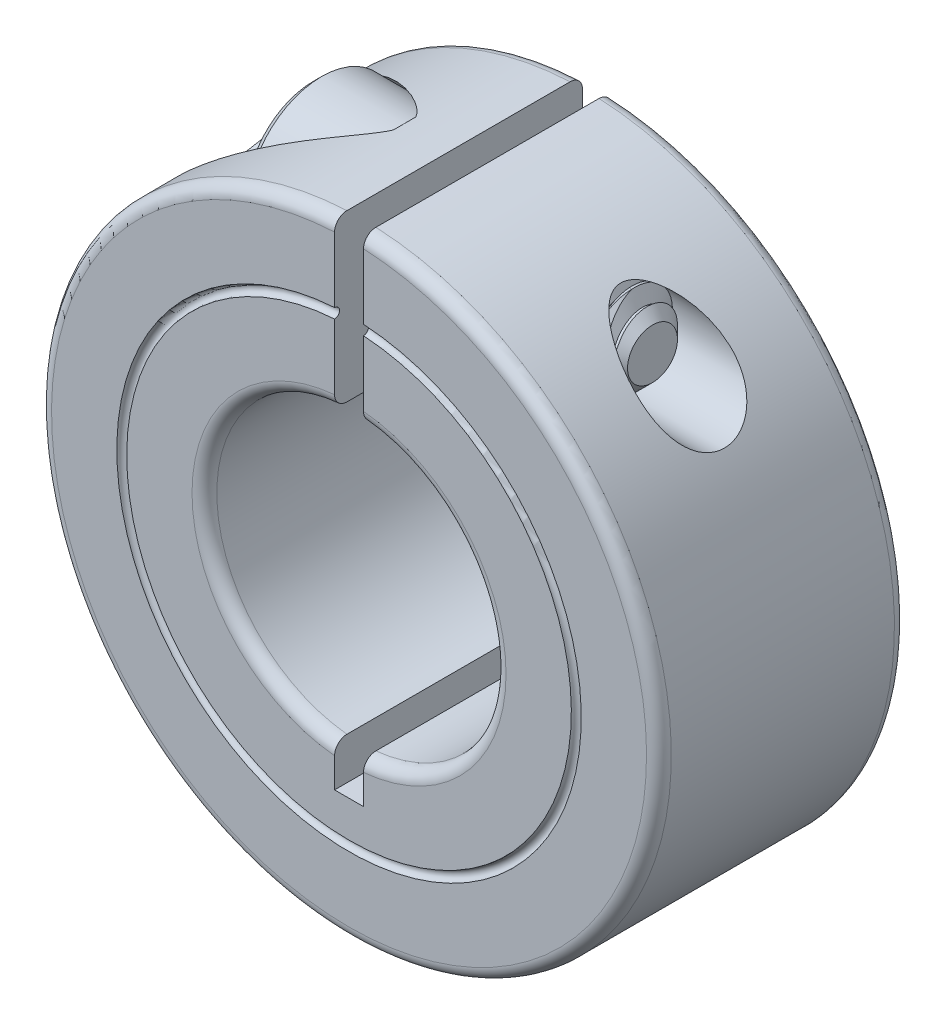
SolidWorks part; units mm, degrees
ref_plane "Front Plane" through (0, 0, 0) normal (0, 0, 1) x (1, 0, 0)
ref_plane "Top Plane" through (0, 0, 0) normal (0, 1, 0) x (1, 0, 0)
ref_plane "Right Plane" through (0, 0, 0) normal (1, 0, 0) x (0, 0, -1)
sketch "Sketch1" plane through (0, 0, 0) normal (0, 0, 1) x (1, 0, 0)
  line L0 (-0.5556, 5.5284) -> (-0.5556, 11.8933)
  line L2 (0.5556, 5.5284) -> (0.5556, 11.8933)
  line L3 (0, 0) -> (0, 5.5284) construction
  line L4 (0.5556, 5.5284) -> (-0.5556, 5.5284) construction
  line L5 (0, -11.9062) -> (0, -5.5562) construction
  line L6 (0, -5.5562) -> (0, -8.7313) construction
  line L7 (-0.5556, -5.5284) -> (-0.5556, -7.1438)
  line L8 (-0.5556, -7.1438) -> (0.5556, -7.1438)
  line L9 (0.5556, -5.5284) -> (0.5556, -7.1438)
  line L10 (-0.5556, 8.7108) -> (0.5556, 8.7108) construction
  circle A0 centre (0, 0) radius 11.9062 construction
  circle A1 centre (0, 0) radius 5.5562 construction
  arc A3 (-0.5556, 11.8933) -> (0.5556, 11.8933) centre (0, 0) ccw
  arc A4 (0.5556, -5.5284) -> (0.5556, 5.5284) centre (0, 0) ccw
  arc A5 (-0.5556, 5.5284) -> (-0.5556, -5.5284) centre (0, 0) ccw
  point P4 (11.9062, 0)
  point P5 (-11.9062, 0)
  point P19 (0, -7.1438)
  dimension "Bore Dia" = 11.1125
  dimension "OD" = 23.8125
  dimension "Separation" = 1.1112
extrude "Extrude1" add sketch "Sketch1" along normal mid plane 9.525
fillet "Fillet1" radius 0.4763 6 edges at (0, -11.9063, -4.7625) (0, -11.9063, 4.7625) (-5.5563, 0, -4.7625) (-5.5563, 0, 4.7625) (5.5562, 0, -4.7625) (5.5562, 0, 4.7625)
sketch "Sketch2" plane through (0, 0, 0) normal (0, 1, 0) x (1, 0, 0)
  line L0 (0, 0) -> (-5.5562, 0) construction
  line L1 (-5.5562, 0) -> (-11.9063, 0) construction
  line L2 (-8.7313, 4.7625) -> (-8.7313, -4.7625) construction
  line L3 (11.43, 4.7625) -> (-11.43, 4.7625) construction
  line L4 (-11.43, -4.7625) -> (11.43, -4.7625) construction
  line L5 (-11.9063, 4.2862) -> (-11.9063, -4.2862) construction
  line L6 (-5.5562, 4.2862) -> (-5.5562, -4.2862) construction
  line L8 (-8.9218, -4.7625) -> (-8.5407, -4.7625)
  line L9 (0, 4.7625) -> (0, -4.7625) construction
  line L10 (-0.5556, 4.7625) -> (-6.0325, 4.7625) construction
  arc A1 (-8.5407, -4.7625) -> (-8.9218, -4.7625) centre (-8.7313, -4.7625) ccw
  point P1 (-8.7313, 0)
  dimension "D2" = 0.1905
revolve "Cut-Revolve1" cut sketch "Sketch2" angle 360 about L9
sketch "Sketch3" plane through (0, 0, 0) normal (0, 0, 1) x (1, 0, 0)
  line L0 (11.9063, 8.7108) -> (-11.9062, 8.7108)
  line L1 (-11.9062, 8.7108) -> (-11.9063, 5.7771)
  line L2 (-11.9063, 5.7771) -> (-2.6289, 5.7771)
  line L4 (-2.6289, 5.7771) -> (-2.6289, 6.9582)
  line L7 (-2.6289, 6.9582) -> (11.9062, 6.9582)
  line L8 (11.9062, 6.9582) -> (11.9063, 8.7108)
  line L9 (-11.9062, 8.7108) -> (-14.84, 8.7108) construction
  line L10 (-0.5556, 8.7108) -> (0.5556, 8.7108) construction
  dimension "D2" = 2.6289
  dimension "D4" = 5.8674
  dimension "Screw Dia" = 3.5052
revolve "Cut-Revolve2" cut sketch "Sketch3" angle 360 about L9
sketch "Sketch4" plane through (0, 0, 0) normal (0, 0, 1) x (1, 0, 0)
  line L0 (-6.1341, 8.7108) -> (-6.1341, 11.581)
  line L2 (-6.1341, 11.581) -> (-2.6289, 11.581)
  line L3 (-2.6289, 11.581) -> (-2.6289, 10.4634)
  line L4 (-2.6289, 10.4634) -> (6.8961, 10.4634)
  line L5 (-2.6289, 5.7771) -> (-2.6289, 6.9582) construction
  line L6 (6.8961, 10.4634) -> (6.8961, 8.7108)
  line L7 (-2.6289, 6.9582) -> (11.9062, 6.9582) construction
  line L8 (6.8961, 8.7108) -> (-6.1341, 8.7108)
  line L9 (6.8961, 10.4634) -> (6.8961, 6.9582) construction
  line L10 (-6.1341, 8.7108) -> (-9.0043, 8.7108) construction
  line L11 (-11.9062, 8.7108) -> (-14.84, 8.7108) construction
  dimension "Head Ht" = 3.5052
  dimension "Screw Lg" = 9.525
  dimension "Head Dia" = 5.7404
revolve "Revolve1" add sketch "Sketch4" angle 360 about L8
sketch "Sketch5" plane through (-6.1341, 0, 0) normal (-1, 0, 0) x (0, -1, 0)
  line L1 (-7.9089, -1.3891) -> (-7.1069, 0)
  line L2 (-7.1069, 0) -> (-7.9089, 1.3891)
  line L3 (-7.9089, 1.3891) -> (-9.5128, 1.3891)
  line L4 (-9.5128, 1.3891) -> (-10.3148, 0)
  line L5 (-10.3148, 0) -> (-9.5128, -1.3891)
  line L6 (-9.5128, -1.3891) -> (-7.9089, -1.3891)
  circle A0 centre (-8.7108, 0) radius 1.3891 construction
  dimension "Hex" = 2.7781
extrude "Cut-Extrude1" cut sketch "Sketch5" against normal blind 2.7781
chamfer "Chamfer1" distance 0.3175 angle 45 1 edges at (-6.1341, 11.581, 0)
sketch "Sketch6" plane through (6.8961, 0, 0) normal (1, 0, 0) x (0, 1, 0)
  circle A0 centre (8.7108, 0) radius 1.7526 construction
  circle A1 centre (8.7108, 0) radius 1.7526
  point P3 (10.4634, 0)
curve "Helix/Spiral1" pitch 0.7937 height 9.525 turns 12 parameters "Height"=9.525, "Pitch"=0.7937
sketch "Sketch7" plane through (0, 0, 0) normal (0, 0, 1) x (1, 0, 0)
  line L0 (7.2434, 9.862) -> (6.8465, 10.5494) construction
  line L1 (6.8465, 10.5494) -> (7.6402, 10.5494) construction
  line L2 (7.6402, 10.5494) -> (7.2434, 9.862) construction
  line L3 (6.8961, 10.4634) -> (7.5906, 10.4634) construction
  line L4 (7.1938, 9.9479) -> (7.293, 9.9479)
  line L5 (7.2434, 10.5494) -> (7.2434, 10.4634) construction
  line L6 (7.2434, 9.9479) -> (7.2434, 9.862) construction
  line L7 (7.1938, 9.9479) -> (6.8713, 10.5064)
  line L8 (6.8713, 10.5064) -> (7.6154, 10.5064)
  line L9 (7.6154, 10.5064) -> (7.293, 9.9479)
  point P10 (7.2434, 10.5064)
  dimension "D1" = 0.7937
  dimension "D2" = 0.0992
chamfer "Chamfer2" distance 0.7937 angle 45 1 edges at (6.8961, 10.4634, 0)
sweep "Cut-Sweep1" cut profiles "Sketch7" path "Helix/Spiral1"
equation "\"D1@Sketch3\" = \"Screw Dia@Sketch3\""
equation "\"D1@Cut-Extrude1\" = \"Hex@Sketch5\""
equation "\"D1@Fillet1\" = \"Width@Extrude1\"*.05"
equation "\"D4@Sketch3\" = \"Head Dia@Sketch4\" + .005"
equation "\"Height@Helix/Spiral1\" = \"Screw Lg@Sketch4\""
equation "\"D1@Sketch7\" = \"Pitch@Helix/Spiral1\""
equation "\"D2@Sketch7\" = \"D1@Sketch7\"/8"
equation "\"D1@Chamfer2\" = \"Pitch@Helix/Spiral1\""
equation "\"Separation@Sketch1\" = \"Bore Dia@Sketch1\"/10"
equation "\"D2@Sketch3\" = \"Screw Dia@Sketch3\"*.750"
